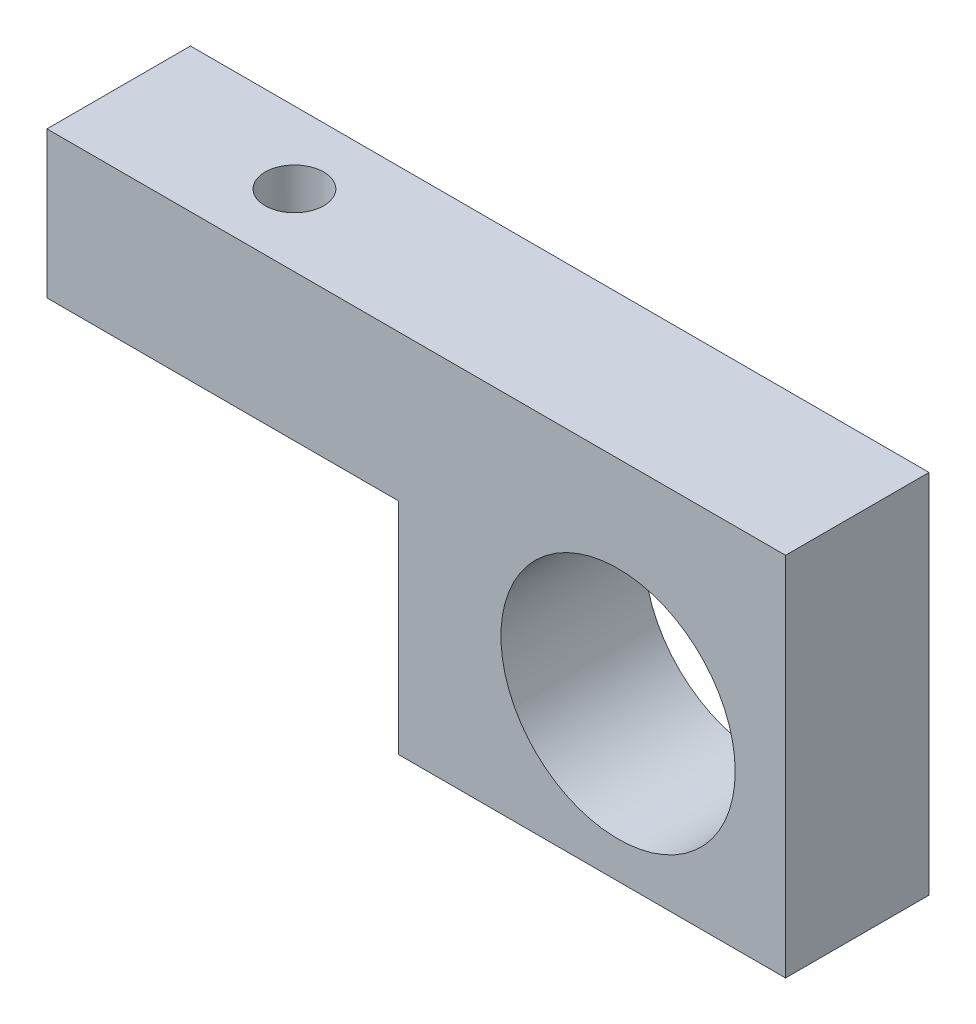
SolidWorks part; units mm, degrees
material "ABS"
ref_plane "Front Plane" through (0, 0, 0) normal (0, 0, 1) x (1, 0, 0)
ref_plane "Top Plane" through (0, 0, 0) normal (0, 1, 0) x (1, 0, 0)
ref_plane "Right Plane" through (0, 0, 0) normal (1, 0, 0) x (0, 0, -1)
sketch "Sketch1" plane through (0, 0, 0) normal (0, 0, 1) x (1, 0, 0)
  line L0 (-24, 15) -> (0, 15)
  line L1 (0, 15) -> (0, 0)
  line L2 (0, 0) -> (93, 0)
  line L3 (93, 0) -> (93, 102.7)
  line L4 (93, 102.7) -> (0, 102.7)
  line L5 (0, 102.7) -> (0, 30)
  line L6 (0, 30) -> (-24, 30)
  line L7 (-24, 30) -> (-24, 15)
  circle A0 centre (15, 10.5) radius 8
  circle A1 centre (70, 72) radius 11
  circle A2 centre (15, 10.5) radius 11
  dimension "D1" = 15
  dimension "D10" = 16
  dimension "D11" = 22
  dimension "D12" = 22
  dimension "D2" = 24
  dimension "D3" = 72.7
  dimension "D4" = 15
  dimension "D5" = 15
  dimension "D6" = 10.5
  dimension "D7" = 82.5061
  dimension "D8" = 72
  dimension "D9" = 93
extrude "Boss-Extrude1" add sketch "Sketch1" along normal blind 4.8 contours A2 L2 L3 L4 L5 L6 L7 L0 L1 A1 | L2 A2 A0 region at (44.5238, 51.0418, 0) region at (8.6656, 19.1141, 0)
sketch "Sketch2" plane through (0, 0, 4.8) normal (0, 0, 1) x (1, 0, 0)
  line L0 (93, 0) -> (93, 102.7) construction
  line L1 (48.1786, 92.7632) -> (93, 92.7632)
  line L2 (48.1786, 92.7632) -> (48.1786, 52.666)
  line L3 (48.1786, 52.666) -> (93, 52.666)
  line L4 (93, 92.7632) -> (93, 52.666)
  line L5 (48.1786, 92.7632) -> (93, 52.666) construction
  line L6 (48.1786, 52.666) -> (93, 92.7632) construction
  circle A0 centre (70, 72) radius 11
  circle A1 centre (70, 72) radius 4.15
  point P8 (70.5893, 72.7146)
  line M4 (93, 0) -> (93, 102.7)
  circle M10 centre (70, 72) radius 11
  dimension "D1" = 22
  dimension "D2" = 8.3
extrude "Boss-Extrude2" add sketch "Sketch2" along normal blind 8.2 contours L2 L3 L1 M4 M10 region at (70.5893, 92.1618, 4.8)
sketch "Sketch3" plane through (0, 0, 4.8) normal (0, 0, 1) x (1, 0, 0)
  line L1 (-24, 15) -> (0, 15)
  line L2 (-24, 15) -> (-24, 30)
  line L3 (-24, 30) -> (0, 30)
  line L4 (0, 15) -> (0, 30)
  line L5 (-24, 15) -> (0, 30) construction
  line L6 (-24, 30) -> (0, 15) construction
  line L7 (0, 0) -> (93, 0)
  line L8 (0, 0) -> (0, 52.666)
  line L9 (0, 52.666) -> (93, 52.666)
  line L10 (93, 0) -> (93, 52.666)
  line L11 (0, 0) -> (93, 52.666) construction
  line L12 (0, 52.666) -> (93, 0) construction
  circle A0 centre (15, 10.5) radius 8
  point P4 (-12, 22.5)
  point P11 (46.5, 26.333)
  circle M1 centre (15, 10.5) radius 8
  line M6 (0, 102.7) -> (0, 30)
  line M7 (0, 30) -> (-24, 30)
  line M8 (-24, 30) -> (-24, 15)
  line M9 (-24, 15) -> (0, 15)
  line M10 (0, 15) -> (0, 0)
  line M11 (0, 0) -> (93, 0)
  line M12 (93, 0) -> (93, 52.666)
  line M13 (93, 52.666) -> (48.1786, 52.666)
extrude "Boss-Extrude3" add sketch "Sketch3" along normal blind 5 contours L4 M9 M7 M8 | L9 L4 M6 M10 M11 M12 M13 M1 region at (-12, 22.5, 4.8) region at (47.8484, 27.0108, 4.8)
sketch "Sketch4" plane through (0, 83.2317, 0) normal (0, -1, 0) x (1, 0, 0)
  line L0 (0, 9.8) -> (0, 4.8) construction
  line L1 (0, 4.8) -> (48.1786, 4.8)
  line L2 (0, 4.8) -> (0, 45.3)
  line L3 (0, 45.3) -> (48.1786, 45.3)
  line L4 (48.1786, 4.8) -> (48.1786, 45.3)
  line L5 (0, 4.8) -> (48.1786, 45.3) construction
  line L6 (0, 45.3) -> (48.1786, 4.8) construction
  line L7 (0, 4.8) -> (48.1786, 4.8) construction
  line L8 (48.1786, 13) -> (48.1786, 9.8) construction
  line L9 (0, 0) -> (93, 0) construction
  line L10 (0, 45.3) -> (-5, 45.3)
  line L11 (0, 45.3) -> (0, 0)
  line L12 (0, 0) -> (-5, 0)
  line L13 (-5, 45.3) -> (-5, 0)
  line L14 (0, 45.3) -> (-5, 0) construction
  line L15 (0, 0) -> (-5, 45.3) construction
  circle A0 centre (13.9465, 30.3) radius 6.35
  circle A1 centre (13.9465, 23.3) radius 18.5
  circle A3 centre (29.4465, 23.3) radius 2
  circle A4 centre (21.6965, 9.8766) radius 2
  circle A5 centre (6.1965, 9.8766) radius 2
  point P10 (24.0893, 25.05)
  point P30 (-2.5, 22.65)
  arc M5 (5.039, 30.9329) -> (22.854, 30.9329) centre (13.9465, 30.3) ccw
  arc M7 (23.1854, 31.0672) -> (4.7077, 31.0672) centre (13.9465, 23.3) cw
  circle M9 centre (21.6965, 9.8766) radius 1.6
  circle M10 centre (6.1965, 9.8766) radius 1.6
  circle M11 centre (-1.5535, 23.3) radius 1.6
  circle M12 centre (6.1965, 36.7234) radius 1.6
  circle M13 centre (21.6965, 36.7234) radius 1.6
  circle M15 centre (27.3699, 31.05) radius 2.1
  circle M16 centre (0.5231, 31.05) radius 2.1
  circle M17 centre (13.9465, 7.8) radius 2.1
  circle M19 centre (13.9465, 23.3) radius 18.5
  dimension "D1" = 12.7
  dimension "D2" = 15
  dimension "D3" = 4
  dimension "D4" = 4
  dimension "D5" = 4
  dimension "D6" = 5
  dimension "D7" = 0
extrude "Boss-Extrude4" add sketch "Sketch4" along normal blind 5 contours L1 L4 L3 M19 | A0 L3 L2 A5 A4 A3 M12 M19 M16 M11 M13 M17 M15 M5 M7 | M5 M7 | M17 | A4 M9 | M9 | M10 | A5 M10 | M15 | L2 M16 | L2 L1 M19 region at (3.3557, 83.2317, 6.6306) region at (34.3643, 83.2317, 27.4815) region at (15.1399, 83.2317, 22.3686) region at (1.1393, 83.2317, 31.05) region at (19.7531, 83.2317, 9.8766) region at (4.2531, 83.2317, 9.8766) region at (21.6965, 83.2317, 9.8766) region at (6.1965, 83.2317, 9.8766) region at (27.3699, 83.2317, 31.05) region at (13.9465, 83.2317, 7.8)
sketch "Sketch5" plane through (48.1786, 0, 0) normal (1, 0, 0) x (0, 0, -1)
  line L0 (-45.3, 83.2317) -> (-13, 92.7632)
  line L1 (-13, 92.7632) -> (-4.8, 92.7632)
  line L2 (-4.8, 92.7632) -> (-4.8, 78.2317)
  line L3 (-4.8, 78.2317) -> (-45.3, 78.2317)
  line L4 (-45.3, 78.2317) -> (-45.3, 83.2317)
extrude "Boss-Extrude5" add sketch "Sketch5" against normal blind 5
sketch "Sketch6" plane through (0, 0, 4.8) normal (0, 0, 1) x (1, 0, 0)
  line L0 (0, 78.2317) -> (0, 52.666) construction
  line L1 (0, 78.2317) -> (48.1786, 78.2317)
  line L2 (0, 78.2317) -> (0, 52.666)
  line L3 (0, 52.666) -> (48.1786, 52.666)
  line L4 (48.1786, 78.2317) -> (48.1786, 52.666)
  line L5 (0, 78.2317) -> (48.1786, 52.666) construction
  line L6 (0, 52.666) -> (48.1786, 78.2317) construction
  line L7 (0, 78.2317) -> (48.1786, 78.2317) construction
  point P4 (24.0893, 65.4489)
extrude "Boss-Extrude6" add sketch "Sketch6" along normal up to surface (5 mm away) up to face at (20.6865, 27.5553, 9.8)
ref_plane "Plane1" through (3.9877, 7.5909, 34.4544) normal (0.9262, 0.2454, -0.2862) x (0.0581, -0.8429, -0.5349)
sketch "Sketch8" plane through (0, 30, 0) normal (0, 1, 0) x (1, 0, 0)
  line L0 (0, 0) -> (-24, -9.8)
  line L1 (-24, -9.8) -> (-24, 0)
  line L2 (-24, 0) -> (0, -9.8)
  circle A0 centre (-12, -4.9) radius 2
  dimension "D1" = 4
extrude "Cut-Extrude1" cut sketch "Sketch8" against normal through all contours A0
sketch "Sketch9" plane through (0, 0, 0) normal (0, 0, -1) x (-1, 0, 0)
  line L1 (0, 30) -> (-93, 30)
  line L2 (0, 30) -> (0, 102.7)
  line L3 (0, 102.7) -> (-93, 102.7)
  line L4 (-93, 30) -> (-93, 102.7)
extrude "Cut-Extrude2" cut sketch "Sketch9" against normal blind 100
sketch "Sketch10" plane through (0, 0, 9.8) normal (0, 0, 1) x (1, 0, 0)
  line L0 (93, 30) -> (-24, 30) construction
  line L1 (93, 0) -> (26.438, 0)
  line L2 (93, 0) -> (93, 30)
  line L3 (93, 30) -> (26.438, 30)
  line L4 (26.438, 0) -> (26.438, 30)
extrude "Cut-Extrude3" cut sketch "Sketch10" against normal blind 100
sketch "Sketch11" plane through (0, 0, 0) normal (0, 0, -1) x (-1, 0, 0)
  line L0 (24, 30) -> (24, 15) construction
  line L1 (0, 15) -> (24, 15)
  line L2 (0, 15) -> (0, 30)
  line L3 (0, 30) -> (24, 30)
  line L4 (24, 15) -> (24, 30)
  line L5 (-26.438, 30) -> (24, 30) construction
extrude "Boss-Extrude7" add sketch "Sketch11" along normal blind 12
sketch "Sketch13" plane through (-24, 0, 0) normal (-1, 0, 0) x (0, 0, 1)
  line L0 (9.8, 30) -> (9.8, 15) construction
  line L1 (-12, 30) -> (9.8, 30)
  line L2 (-12, 30) -> (-12, 25)
  line L3 (-12, 25) -> (9.8, 25)
  line L4 (9.8, 30) -> (9.8, 25)
  dimension "D1" = 5
extrude "Cut-Extrude4" cut sketch "Sketch13" against normal blind 200
sketch "Sketch15" plane through (0, 25, 0) normal (0, 1, 0) x (1, 0, 0)
  circle A0 centre (-12, 5.1) radius 2
  circle A1 centre (-12, -4.9) radius 2 construction
  dimension "D1" = 4
  dimension "D2" = 10
  dimension "D3" = 0
extrude "Cut-Extrude5" cut sketch "Sketch15" against normal blind 200
sketch "Sketch16" plane through (0, 25, 0) normal (0, 1, 0) x (1, 0, 0)
  line L1 (0, 0) -> (-24, 0)
  line L2 (0, 0) -> (0, 12)
  line L3 (0, 12) -> (-24, 12)
  line L4 (-24, 0) -> (-24, 12)
extrude "Cut-Extrude6" cut sketch "Sketch16" against normal blind 10
